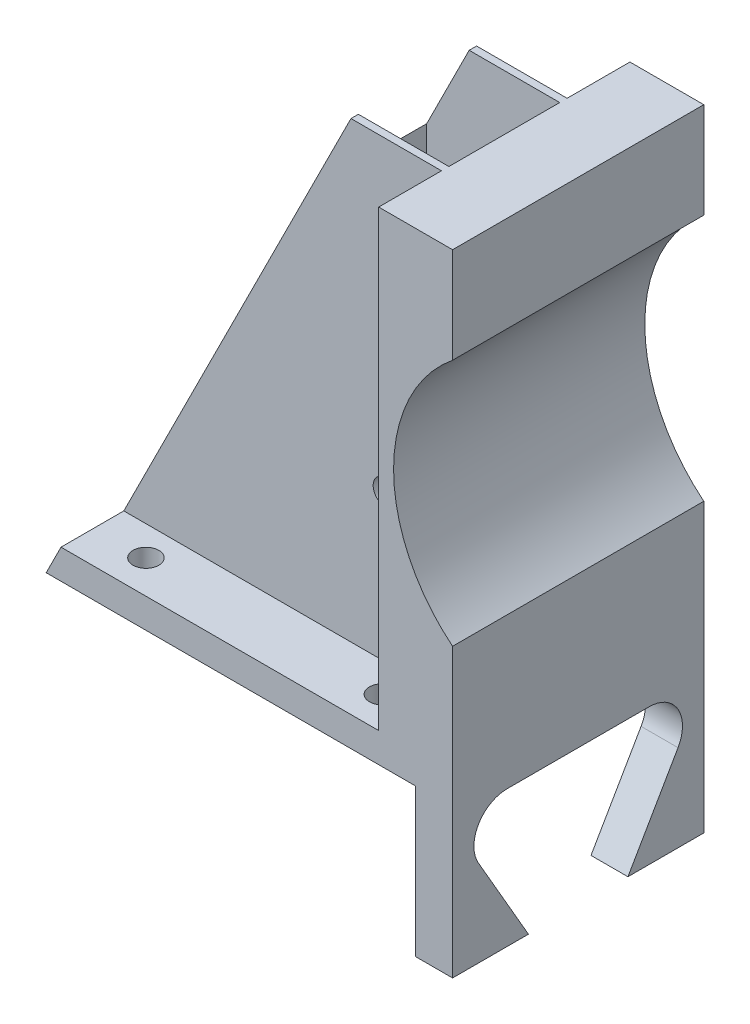
SolidWorks part; units mm, degrees
ref_plane "Front Plane" through (0, 0, 0) normal (0, 0, 1) x (1, 0, 0)
ref_plane "Top Plane" through (0, 0, 0) normal (0, 1, 0) x (1, 0, 0)
ref_plane "Right Plane" through (0, 0, 0) normal (1, 0, 0) x (0, 0, -1)
sketch "Sketch4" plane through (0, 0, 0) normal (0, 0, 1) x (1, 0, 0)
  line L0 (-25, -10) -> (30, -10)
  line L1 (-25, -10) -> (25, -10) construction
  line L2 (-25, -10) -> (-25, 10) construction
  line L3 (-25, 10) -> (25, 10) construction
  line L4 (25, -10) -> (25, 10) construction
  line L5 (-25, -10) -> (25, 10) construction
  line L6 (-25, 10) -> (25, -10) construction
  line L7 (30, -10) -> (30, 28.8794)
  line L8 (30, 62.4074) -> (30, 75.3614)
  line L9 (30, 75.3614) -> (7.7472, 75.3614)
  line L10 (7.7472, 75.3614) -> (-25, 10)
  line L11 (-25, 10) -> (-25, -10)
  arc A0 (30, 62.4074) -> (30, 28.8794) centre (43.605, 45.6434) ccw
  point P0 (0, 0)
  dimension "D3" = 21.59
  dimension "D4" = 12.954
  dimension "D1" = 50
  dimension "D2" = 20
  dimension "D5" = 33.528
  dimension "D6" = 5
extrude "Boss-Extrude2" add sketch "Sketch4" along normal blind 34
sketch "Sketch5" plane through (0, 0, 34) normal (0, 0, 1) x (1, 0, 0)
  line L0 (-22.9959, 14) -> (7.7472, 75.3614)
  line L1 (-25, -10) -> (25, -10)
  line L2 (-25, -10) -> (-25, 10)
  line L3 (-25, 10) -> (25, 10)
  line L4 (25, -10) -> (25, 10)
  line L5 (7.7472, 75.3614) -> (-25, 10) construction
  line L6 (7.7472, 75.3614) -> (20, 75.3614)
  line L7 (30, 75.3614) -> (7.7472, 75.3614) construction
  line L8 (20, 75.3614) -> (20, 14)
  line L9 (20, 14) -> (-22.9959, 14)
  dimension "D1" = 50
  dimension "D2" = 20
  dimension "D3" = 4
  dimension "D4" = 45
extrude "Cut-Extrude1" cut sketch "Sketch5" against normal blind 8.5
sketch "Sketch6" plane through (0, 0, 0) normal (0, 0, -1) x (-1, 0, 0)
  line L0 (22.9959, 14) -> (-20, 14)
  line L1 (25, -10) -> (-25, -10)
  line L2 (25, -10) -> (25, 10)
  line L3 (25, 10) -> (-25, 10)
  line L4 (-25, -10) -> (-25, 10)
  line L5 (-7.7472, 75.3614) -> (25, 10) construction
  line L6 (-20, 14) -> (-20, 75.3614)
  line L7 (-30, 75.3614) -> (-7.7472, 75.3614) construction
  line L8 (-20, 75.3614) -> (-7.7472, 75.3614)
  line L9 (-7.7472, 75.3614) -> (22.9959, 14)
  dimension "D1" = 50
  dimension "D2" = 20
  dimension "D3" = 45
  dimension "D4" = 4
extrude "Cut-Extrude2" cut sketch "Sketch6" against normal blind 8.5
sketch "Sketch7" plane through (0, 0, 8.5) normal (0, 0, -1) x (-1, 0, 0)
  line L1 (-25, 10) -> (27.0063, 10)
  line L2 (-25, 10) -> (-25, -11.6279)
  line L3 (-25, -11.6279) -> (27.0063, -11.6279)
  line L4 (27.0063, 10) -> (27.0063, -11.6279)
  dimension "D1" = 21.6279
  dimension "D2" = 52.0063
extrude "Cut-Extrude3" cut sketch "Sketch7" against normal through all
sketch "Sketch8" plane through (30, 0, 0) normal (1, 0, 0) x (0, 0, -1)
  line L0 (-26.61, 8) -> (-7.38, 8)
  line L1 (-29.7004, 2.8571) -> (-19.979, -15.4295)
  line L2 (-14.011, -15.4295) -> (-4.2896, 2.8571)
  line L3 (-34, -10) -> (-34, 28.8794) construction
  line L5 (0, -10) -> (0, 28.8794) construction
  line L6 (-34, -10) -> (0, -10) construction
  line L7 (-34, -10) -> (-34, 10) construction
  line L8 (-34, 10) -> (0, 10) construction
  line L9 (0, -10) -> (0, 10) construction
  line L10 (-26.61, 4.5) -> (-7.38, 4.5) construction
  line L11 (-24.295, -13.8431) -> (-10.3108, -13.8431) construction
  arc A3 (-26.61, 8) -> (-29.7004, 2.8571) centre (-26.61, 4.5) ccw
  arc A4 (-7.38, 8) -> (-4.2896, 2.8571) centre (-7.38, 4.5) cw
  arc A5 (-14.011, -15.4295) -> (-19.979, -15.4295) centre (-16.995, -13.8431) cw
  dimension "D1" = 3.5
  dimension "D2" = 3.5
  dimension "D3" = 3.3794
  dimension "D4" = 19.23
  dimension "D5" = 20.71
  dimension "D6" = 20.71
  dimension "D7" = 7.39
  dimension "D8" = 2
  dimension "D9" = 20
sketch "Sketch9" plane through (30, 0, 0) normal (1, 0, 0) x (0, 0, -1)
  line L0 (-26.615, 7.4897) -> (-7.385, 7.4897) construction
  line L1 (-4.3541, 2.2394) -> (-13.9691, -14.4106) construction
  line L2 (-29.6459, 2.2394) -> (-20.0309, -14.4106) construction
  line L4 (-34, 28.8794) -> (0, 28.8794) construction
  line L5 (-26.615, 3.9897) -> (-7.385, 3.9897) construction
  line L6 (-17, 3.9897) -> (-17, -12.6603) construction
  line L7 (-34, 9.4397) -> (0, 9.4397) construction
  line L8 (-34, -10) -> (-34, 28.8794) construction
  line L9 (0, -10) -> (0, 28.8794) construction
  line L10 (-26.615, 8.4897) -> (-7.385, 8.4897)
  line L11 (-3.4881, 1.7393) -> (-13.1031, -14.9107)
  line L12 (-30.5119, 1.7393) -> (-20.8969, -14.9107)
  arc A0 (-26.615, 7.4897) -> (-29.6459, 2.2394) centre (-26.615, 3.9897) ccw construction
  arc A1 (-4.3541, 2.2394) -> (-7.385, 7.4897) centre (-7.385, 3.9897) ccw construction
  arc A2 (-20.0309, -14.4106) -> (-13.9691, -14.4106) centre (-17, -12.6603) ccw construction
  arc A3 (-29.6459, 2.2394) -> (-26.615, 7.4897) centre (-26.615, 3.9897) ccw construction
  arc A4 (-7.385, 7.4897) -> (-4.3541, 2.2394) centre (-7.385, 3.9897) ccw construction
  arc A5 (-13.9691, -14.4106) -> (-20.0309, -14.4106) centre (-17, -12.6603) ccw construction
  arc A6 (-3.4881, 1.7393) -> (-7.385, 8.4897) centre (-7.385, 3.9897) ccw
  arc A7 (-20.8969, -14.9107) -> (-13.1031, -14.9107) centre (-17, -12.6603) ccw
  arc A8 (-26.615, 8.4897) -> (-30.5119, 1.7393) centre (-26.615, 3.9897) ccw
  point P21 (-17, 28.8794)
  dimension "D1" = 7
  dimension "D2" = 7
  dimension "D3" = 7
  dimension "D4" = 19.23
  dimension "D5" = 16.65
  dimension "D6" = 1.95
  dimension "D7" = 22.1
  dimension "D8" = 1
extrude "Cut-Extrude4" cut sketch "Sketch9" against normal through all
sketch "Sketch10" plane through (0, 10, 0) normal (0, -1, 0) x (1, 0, 0)
  line L0 (25, 23.7327) -> (25, 34) construction
  line L1 (25, 34) -> (-25, 34) construction
  line L3 (-25, 0) -> (25, 0) construction
  line L4 (-25, 34) -> (-25, 0) construction
  circle A0 centre (16, 29.5) radius 1.75
  circle A1 centre (16, 4.5) radius 1.75
  circle A2 centre (-16, 29.5) radius 1.75
  circle A3 centre (-16, 4.5) radius 1.75
  dimension "D3" = 3.5
  dimension "D4" = 3.5
  dimension "D6" = 4.5
  dimension "D7" = 4.5
  dimension "D8" = 4.5
  dimension "D10" = 3.5
  dimension "D11" = 3.5
  dimension "D1" = 25
  dimension "D2" = 9
  dimension "D5" = 4.5
  dimension "D9" = 9
  dimension "D12" = 9
extrude "Cut-Extrude5" cut sketch "Sketch10" against normal blind 10
sketch "Sketch14" plane through (20, 0, 0) normal (-1, 0, 0) x (0, 0, 1)
  line L0 (25.5, 75.3614) -> (8.5, 75.3614) construction
  line L1 (9.5, 75.3614) -> (24.5, 75.3614)
  line L2 (9.5, 75.3614) -> (9.5, 38.3614)
  line L3 (9.5, 38.3614) -> (24.5, 38.3614)
  line L4 (24.5, 75.3614) -> (24.5, 38.3614)
  line L5 (8.5, 75.3614) -> (8.5, 14) construction
  dimension "D1" = 15
  dimension "D2" = 1
  dimension "D3" = 37
extrude "Cut-Extrude8" cut sketch "Sketch14" along normal blind 18
sketch "Sketch15" plane through (0, 38.3614, 0) normal (0, 1, 0) x (1, 0, 0)
  line L1 (2, -9.5) -> (20, -9.5)
  line L2 (2, -9.5) -> (2, -24.5)
  line L3 (2, -24.5) -> (20, -24.5)
  line L4 (20, -9.5) -> (20, -24.5)
extrude "Cut-Extrude9" cut sketch "Sketch15" against normal blind 9
sketch "Sketch16" plane through (20, 0, 0) normal (-1, 0, 0) x (0, 0, 1)
  line L1 (10.5, 38.3614) -> (23.5, 38.3614)
  line L2 (10.5, 38.3614) -> (10.5, 29.3614)
  line L3 (10.5, 29.3614) -> (23.5, 29.3614)
  line L4 (23.5, 38.3614) -> (23.5, 29.3614)
  line L5 (24.5, 75.3614) -> (9.5, 75.3614) construction
  line L6 (8.5, 75.3614) -> (8.5, 14) construction
  dimension "D1" = 46
  dimension "D2" = 37
  dimension "D3" = 13
  dimension "D4" = 2
extrude "Cut-Extrude10" cut sketch "Sketch16" along normal through all
sketch "Sketch17" plane through (0, 0, 25.5) normal (0, 0, 1) x (1, 0, 0)
  line L0 (2, 29.3614) -> (20, 29.3614) construction
  line L1 (20, 14) -> (20, 75.3614) construction
  circle A0 centre (12.5, 33.8614) radius 1.75
  dimension "D1" = 3.5
  dimension "D2" = 4.5
  dimension "D3" = 7.5
extrude "Cut-Extrude11" cut sketch "Sketch17" against normal through all
equation "\"D1@Sketch9\"=3.5*2mm"
